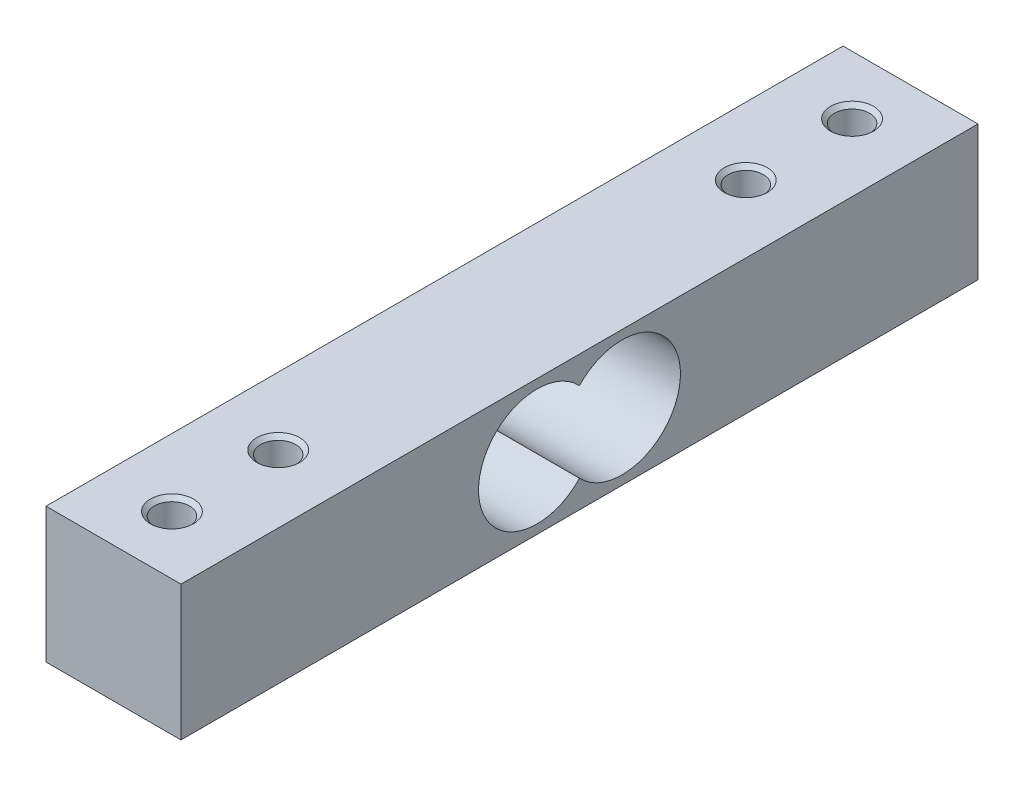
SolidWorks part; units mm, degrees
ref_plane "Plano frontal" through (0, 0, 0) normal (0, 0, 1) x (1, 0, 0)
ref_plane "Plano superior" through (0, 0, 0) normal (0, 1, 0) x (1, 0, 0)
ref_plane "Plano direito" through (0, 0, 0) normal (1, 0, 0) x (0, 0, -1)
sketch "Esboço2" plane through (0, 0, 0) normal (0, 0, 1) x (1, 0, 0)
  line L1 (-6.35, 6.35) -> (6.35, 6.35)
  line L2 (-6.35, 6.35) -> (-6.35, -6.35)
  line L3 (-6.35, -6.35) -> (6.35, -6.35)
  line L4 (6.35, 6.35) -> (6.35, -6.35)
  line L5 (-6.35, 6.35) -> (6.35, -6.35) construction
  line L6 (-6.35, -6.35) -> (6.35, 6.35) construction
  point P0 (0, 0)
  dimension "D1" = 12.7
extrude "Ressalto-extrusão2" add sketch "Esboço2" against normal blind 75
sketch "Esboço3" plane through (6.35, 0, 0) normal (1, 0, 0) x (0, 0, -1)
  line L0 (37.5, 6.35) -> (37.5, -6.35) construction
  line L1 (75, 6.35) -> (0, 6.35) construction
  line L2 (75, -6.35) -> (0, -6.35) construction
  arc A0 (37.5, -3.7749) -> (37.5, 3.7749) centre (41.5, 0) ccw
  arc A1 (37.5, -3.7749) -> (37.5, 3.7749) centre (33.5, 0) cw
  point P8 (45.1716, 0)
  dimension "D1" = 11
  dimension "D2" = 4
  dimension "D3" = 6.35
extrude "Corte-extrusão1" cut sketch "Esboço3" against normal through all
hole_wizard "Furo roscado de M41" positions "Esboço4" profile "Esboço5" tap size "M4" standard "DIN" end condition through all
sketch "Esboço4" plane through (0, 6.35, 0) normal (0, 1, 0) x (1, 0, 0)
  line L0 (-6.35, 37.5) -> (6.35, 37.5) construction
  point P0 (0, 5.5)
  point P2 (0, 15.5)
  point P4 (0, 59.5)
  point P6 (0, 69.5)
  dimension "D1" = 44
  dimension "D2" = 64
  dimension "D3" = 22
  dimension "D4" = 32
sketch "Esboço5" plane through (0, 6.35, -5.5) normal (1, 0, 0) x (0, 0, 1)
  line L0 (0, 0) -> (0, 12.7)
  line L1 (0, 12.7) -> (1.65, 12.7)
  line L2 (1.65, 12.7) -> (1.65, 0.375)
  line L3 (1.65, 0.375) -> (2.025, 0)
  line L5 (2.025, 0) -> (0, 0)
  line L6 (-1.65, 0.375) -> (-2.025, 0) construction
  line L11 (0, -6.35) -> (0, 107.95) construction
  dimension "Thru Tap Drill Dia." = 3.3
  dimension "Thru Tap Drill Depth" = 12.7
  dimension "Near C'Sink Dia." = 4.05
  dimension "Near C'Sink Angle" = 90
cosmetic thread "Rosca de furo1" parameters "D2"=4
cosmetic thread "Rosca de furo2" parameters "D2"=4
cosmetic thread "Rosca de furo3" parameters "D2"=4
cosmetic thread "Rosca de furo4" parameters "D2"=4
